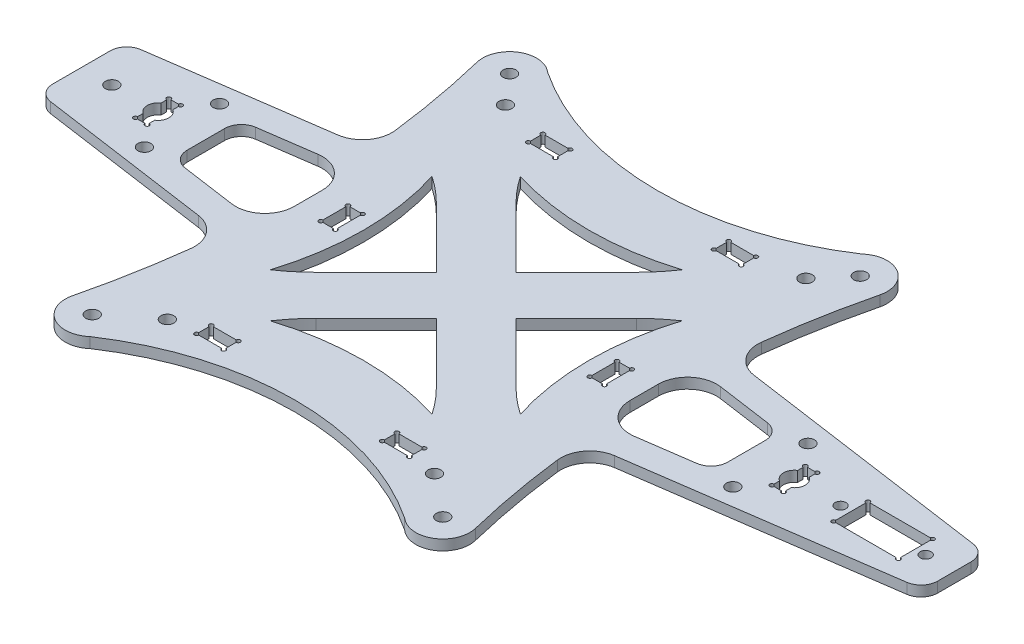
SolidWorks part; units mm, degrees
material "PPS"
ref_plane "前视基准面" through (0, 0, 0) normal (0, 0, 1) x (1, 0, 0)
ref_plane "上视基准面" through (0, 0, 0) normal (0, 1, 0) x (1, 0, 0)
ref_plane "右视基准面" through (0, 0, 0) normal (1, 0, 0) x (0, 0, -1)
sketch "草图1" plane through (0, 0, 0) normal (0, 1, 0) x (1, 0, 0)
  line L3 (-133.7177, 0) -> (146.3754, 0) construction
  line L56 (0, 96.0639) -> (0, -115.1457) construction
  line L65 (-25.5, 41.5) -> (-19, 41.5)
  line L66 (-34, 3.25) -> (-30.5, 3.25)
  line L70 (-34, 3.25) -> (-34, -3.25)
  line L76 (-34, -3.25) -> (-30.5, -3.25)
  line L80 (-30.5, 3.25) -> (-30.5, -3.25)
  line L81 (-25.5, -38) -> (-19, -38)
  line L82 (-25.5, -38) -> (-25.5, -41.5)
  line L83 (-25.5, -41.5) -> (-19, -41.5)
  line L84 (-19, -38) -> (-19, -41.5)
  line L85 (-19, 38) -> (-19, 41.5)
  line L86 (-25.5, 38) -> (-19, 38)
  line L142 (-25.5, 38) -> (-25.5, 41.5)
  line L143 (25.5, 38) -> (25.5, 41.5)
  line L144 (25.5, 38) -> (19, 38)
  line L145 (19, 38) -> (19, 41.5)
  line L146 (19, -38) -> (19, -41.5)
  line L147 (25.5, -41.5) -> (19, -41.5)
  line L148 (25.5, -38) -> (25.5, -41.5)
  line L149 (25.5, -38) -> (19, -38)
  line L150 (30.5, 3.25) -> (30.5, -3.25)
  line L151 (34, -3.25) -> (30.5, -3.25)
  line L152 (34, 3.25) -> (34, -3.25)
  line L153 (34, 3.25) -> (30.5, 3.25)
  line L154 (25.5, 41.5) -> (19, 41.5)
  line L155 (77.65, -2.1518) -> (77.65, -4)
  line L156 (74.85, 4) -> (77.65, 4)
  line L157 (74.85, 4) -> (74.85, 2.1768)
  line L158 (74.85, -4) -> (77.65, -4)
  line L159 (77.65, 4) -> (77.65, 2.1518)
  line L160 (74.85, -2.1768) -> (74.85, -4)
  line L161 (97.5, 7.6653) -> (97.5, -9.1503) construction
  line L162 (89.75, 4.1) -> (105.25, 4.1)
  line L163 (89.75, 4.1) -> (89.75, -4.1)
  line L164 (89.75, -4.1) -> (105.25, -4.1)
  line L165 (105.25, 4.1) -> (105.25, -4.1)
  line L166 (-97.5, 7.6653) -> (-97.5, -9.1503) construction
  line L171 (-74.85, -2.1768) -> (-74.85, -4)
  line L172 (-77.65, 4) -> (-77.65, 2.1518)
  line L173 (-74.85, -4) -> (-77.65, -4)
  line L174 (-74.85, 4) -> (-74.85, 2.1768)
  line L175 (-74.85, 4) -> (-77.65, 4)
  line L176 (-77.65, -2.1518) -> (-77.65, -4)
  line L177 (114.5911, 7.4683) -> (114.5911, -7.4683)
  line L178 (114.5911, 7.4683) -> (43.1936, 17.6463)
  line L179 (114.5911, -7.4683) -> (43.1936, -17.6463)
  line L183 (-23.978, 14.4296) -> (-9.5485, 0)
  line L184 (14.4296, 23.978) -> (0, 9.5485)
  line L185 (-23.978, -14.4296) -> (-9.5485, 0)
  line L186 (-14.4296, 23.978) -> (0, 9.5485)
  line L187 (23.978, -14.4296) -> (9.5485, 0)
  line L188 (23.978, 14.4296) -> (9.5485, 0)
  line L189 (-14.4296, -23.978) -> (0, -9.5485)
  line L190 (14.4296, -23.978) -> (0, -9.5485)
  line L191 (-94.5795, 10.321) -> (-94.5795, -10.321)
  line L192 (-43.1936, 17.6463) -> (-94.5795, 10.321)
  line L193 (-94.5795, -10.321) -> (-43.1936, -17.6463)
  line L195 (-64.75, -7.9571) -> (-64.75, 7.9571)
  line L196 (-64.75, 7.9571) -> (-40.25, 11.4497)
  line L197 (-40.25, 11.4497) -> (-40.25, -11.4497)
  line L198 (-64.75, -7.9571) -> (-40.25, -11.4497)
  line L199 (64.75, 7.9571) -> (40.25, 11.4497)
  line L200 (40.25, 11.4497) -> (40.25, -11.4497)
  line L201 (64.75, -7.9571) -> (40.25, -11.4497)
  line L202 (64.75, 7.9571) -> (64.75, -7.9571)
  circle A0 centre (-36, 43) radius 1.55
  circle A1 centre (-32, -42) radius 1.55
  circle A2 centre (32, -42) radius 1.55
  circle A3 centre (36, 43) radius 1.55
  circle A4 centre (42, 50) radius 1.55
  circle A5 centre (42, -50) radius 1.55
  circle A6 centre (-42, -50) radius 1.55
  circle A7 centre (-42, 50) radius 1.55
  arc A8 (74.85, 2.1768) -> (74.85, -2.1768) centre (76.2307, 0) ccw
  arc A9 (77.65, -2.1518) -> (77.65, 2.1518) centre (76.2307, 0) ccw
  circle A10 centre (107.7, 0) radius 1.3
  circle A11 centre (87.3, 0) radius 1.3
  circle A12 centre (-87.3, 0) radius 1.3 construction
  arc A14 (-77.65, -2.1518) -> (-77.65, 2.1518) centre (-76.2307, 0) cw
  arc A15 (-74.85, 2.1768) -> (-74.85, -2.1768) centre (-76.2307, 0) cw
  arc A18 (-37.7098, 54.831) -> (37.7098, 54.831) centre (0, 111.5317) ccw
  arc A20 (48.2756, 48.4632) -> (43.1936, 17.6463) centre (246.1791, 0) ccw
  arc A21 (48.2756, 48.4632) -> (37.7098, 54.831) centre (42, 50) ccw
  arc A22 (-37.7098, -54.831) -> (37.7098, -54.831) centre (0, -111.5317) cw
  arc A23 (48.2756, -48.4632) -> (43.1936, -17.6463) centre (246.1791, 0) cw
  arc A24 (48.2756, -48.4632) -> (37.7098, -54.831) centre (42, -50) cw
  arc A26 (-48.2756, -48.4632) -> (-37.7098, -54.831) centre (-42, -50) ccw
  arc A27 (-48.2756, -48.4632) -> (-43.1936, -17.6463) centre (-246.1791, 0) ccw
  arc A28 (-48.2756, 48.4632) -> (-37.7098, 54.831) centre (-42, 50) cw
  arc A30 (-48.2756, 48.4632) -> (-43.1936, 17.6463) centre (-246.1791, 0) cw
  arc A31 (-23.978, 14.4296) -> (-29.9602, 19.3706) centre (-52.8883, -14.4807) ccw
  arc A32 (-23.978, -14.4296) -> (-29.9602, -19.3706) centre (-52.8883, 14.4807) cw
  arc A33 (-29.9602, -19.3706) -> (-29.9602, 19.3706) centre (-91.9966, 0) ccw
  arc A34 (-14.4296, 23.978) -> (-19.3706, 29.9602) centre (14.4807, 52.8883) cw
  arc A35 (-19.3706, 29.9602) -> (19.3706, 29.9602) centre (0, 91.9966) ccw
  arc A36 (14.4296, 23.978) -> (19.3706, 29.9602) centre (-14.4807, 52.8883) ccw
  arc A37 (23.978, 14.4296) -> (29.9602, 19.3706) centre (52.8883, -14.4807) cw
  arc A38 (29.9602, 19.3706) -> (29.9602, -19.3706) centre (91.9966, 0) ccw
  arc A39 (23.978, -14.4296) -> (29.9602, -19.3706) centre (52.8883, 14.4807) ccw
  arc A40 (14.4296, -23.978) -> (19.3706, -29.9602) centre (-14.4807, -52.8883) cw
  arc A41 (19.3706, -29.9602) -> (-19.3706, -29.9602) centre (0, -91.9966) ccw
  arc A42 (-14.4296, -23.978) -> (-19.3706, -29.9602) centre (14.4807, -52.8883) ccw
  circle A43 centre (70.5, 9) radius 1.55
  circle A44 centre (70.5, -9) radius 1.55
  circle A45 centre (-70.5, -9) radius 1.55
  circle A46 centre (-70.5, 9) radius 1.55
  circle A47 centre (-87.3, 0) radius 1.55
  point P81 (-34, 0)
  point P118 (0, 0)
  point P140 (-40.25, 0)
  point P149 (-64.75, 0)
  dimension "D5" = 38
  dimension "D18" = 8.2
  dimension "D24" = 3.1
  dimension "D6" = 3.1
  dimension "D11" = 50
  dimension "D15" = 74.85
  dimension "D16" = 2.6
  dimension "D17" = 15.5
  dimension "D21" = 3.1
  dimension "D1" = 6.5
  dimension "D2" = 3.5
  dimension "D3" = 30.5
  dimension "D4" = 19
  dimension "D7" = 32
  dimension "D8" = 42
  dimension "D9" = 43
  dimension "D10" = 36
  dimension "D12" = 42
  dimension "D13" = 2.8
  dimension "D14" = 4
  dimension "D19" = 2.45
  dimension "D20" = 97.5
  dimension "D22" = 9
  dimension "D23" = 70.5
  dimension "D25" = 6.55
  dimension "D26" = 5.75
  dimension "D27" = 6.25
  dimension "D28" = 4
extrude "凸台-拉伸1" add sketch "草图1" along normal blind 2.5
fillet "圆角1" radius 4 8 edges at (114.5911, 1.25, -7.4683) (114.5911, 1.25, 7.4683) (-94.5795, 1.25, 10.321) (-94.5795, 1.25, -10.321) (-64.75, 1.25, 7.9571) (-64.75, 1.25, -7.9571) (64.75, 1.25, 7.9571) (64.75, 1.25, -7.9571)
fillet "圆角2" radius 7 8 edges at (43.1936, 1.25, -17.6463) (43.1936, 1.25, 17.6463) (-43.1936, 1.25, 17.6463) (-43.1936, 1.25, -17.6463) (40.25, 1.25, 11.4497) (40.25, 1.25, -11.4497) (-40.25, 1.25, 11.4497) (-40.25, 1.25, -11.4497)
sketch "草图2" plane through (0, 2.5, 0) normal (0, 1, 0) x (1, 0, 0)
  line L0 (0, 0) -> (0, -66.7571) construction
  circle A0 centre (-77.65, 4) radius 0.5
  circle A1 centre (-74.85, 4) radius 0.5
  circle A2 centre (-77.65, -4) radius 0.5
  circle A3 centre (-74.85, -4) radius 0.5
  circle A4 centre (-25.5, 41.5) radius 0.5
  circle A5 centre (-19, 41.5) radius 0.5
  circle A6 centre (-25.5, 38) radius 0.5
  circle A7 centre (-19, 38) radius 0.5
  circle A8 centre (-34, 3.25) radius 0.5
  circle A9 centre (-30.5, 3.25) radius 0.5
  circle A10 centre (-34, -3.25) radius 0.5
  circle A11 centre (-30.5, -3.25) radius 0.5
  circle A12 centre (-25.5, -38) radius 0.5
  circle A13 centre (-19, -38) radius 0.5
  circle A14 centre (-25.5, -41.5) radius 0.5
  circle A15 centre (-19, -41.5) radius 0.5
  circle A16 centre (19, -41.5) radius 0.5
  circle A17 centre (25.5, -41.5) radius 0.5
  circle A18 centre (19, -38) radius 0.5
  circle A19 centre (25.5, -38) radius 0.5
  circle A20 centre (30.5, -3.25) radius 0.5
  circle A21 centre (34, -3.25) radius 0.5
  circle A22 centre (30.5, 3.25) radius 0.5
  circle A23 centre (34, 3.25) radius 0.5
  circle A24 centre (19, 38) radius 0.5
  circle A25 centre (25.5, 38) radius 0.5
  circle A26 centre (19, 41.5) radius 0.5
  circle A27 centre (25.5, 41.5) radius 0.5
  circle A28 centre (74.85, -4) radius 0.5
  circle A29 centre (77.65, -4) radius 0.5
  circle A30 centre (74.85, 4) radius 0.5
  circle A31 centre (77.65, 4) radius 0.5
  circle A32 centre (89.75, 4.1) radius 0.5
  circle A33 centre (105.25, 4.1) radius 0.5
  circle A34 centre (89.75, -4.1) radius 0.5
  circle A35 centre (105.25, -4.1) radius 0.5
  dimension "D1" = 1
extrude "直角约束" cut sketch "草图2" against normal through all
